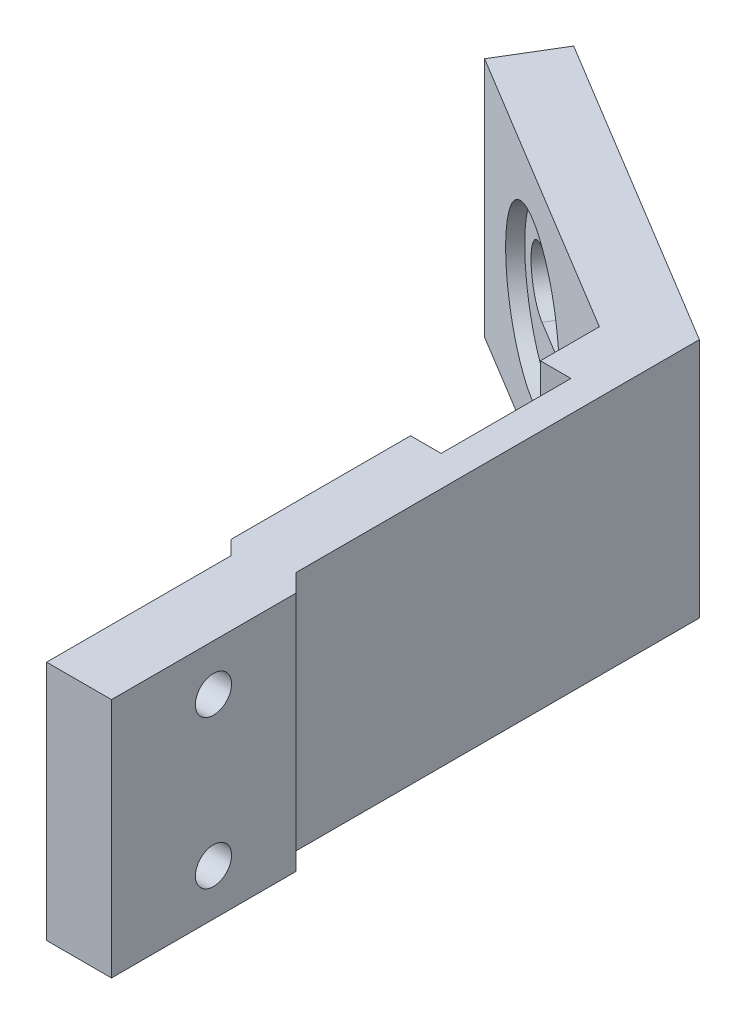
SolidWorks part; units mm, degrees
ref_plane "Front Plane" through (0, 0, 0) normal (0, 0, 1) x (1, 0, 0)
ref_plane "Top Plane" through (0, 0, 0) normal (0, 1, 0) x (1, 0, 0)
ref_plane "Right Plane" through (0, 0, 0) normal (1, 0, 0) x (0, 0, -1)
ref_plane "PY -20.700" through (0, -20.7, 0) normal (0, 1, 0) x (1, 0, 0)
sketch "leg and pad sketch" plane through (0, -20.7, 0) normal (0, 1, 0) x (1, 0, 0)
  line L0 (0.4, 29.7586) -> (0.4, -9.98)
  line L1 (0.4, -9.98) -> (1.92, -11.5)
  line L2 (1.92, -11.5) -> (1.92, -31.37)
  line L3 (1.92, -31.37) -> (8.92, -31.37)
  line L4 (8.92, -31.37) -> (8.92, -11.5)
  line L5 (8.92, -11.5) -> (7, -9.58)
  line L6 (7, -9.58) -> (7, 33.9514)
  line L7 (7, 33.9514) -> (-27.2048, 54.5947)
  line L8 (-27.2048, 54.5947) -> (-30.8218, 48.6015)
  line L9 (-30.8218, 48.6015) -> (0.4, 29.7586)
extrude "leg and pad" add sketch "leg and pad sketch" along normal mid plane 26
ref_plane "PX 1.350" through (1.35, 0, 0) normal (1, 0, 0) x (0, 0, -1)
sketch "screw head relief sketch" plane through (1.35, 0, 0) normal (1, 0, 0) x (0, 0, -1)
  line L0 (23.4, -12.7) -> (23.4, -6.7)
  line L1 (23.4, -6.7) -> (9.4, -6.7)
  line L2 (9.4, -6.7) -> (9.4, -12.7)
  line L3 (9.4, -12.7) -> (23.4, -12.7)
extrude "screw head relief" cut sketch "screw head relief sketch" against normal mid plane 4.7
sketch "insert flange relief sketch" plane through (0, -20.7, 0) normal (0, 1, 0) x (1, 0, 0)
  line L0 (-18.3249, 39.8914) -> (-17.0331, 42.0318)
  line L1 (-17.0331, 42.0318) -> (-9.7557, 37.6398)
  line L2 (-9.7557, 37.6398) -> (-11.0475, 35.4994)
  line L3 (-11.0475, 35.4994) -> (-18.3249, 39.8914)
revolve "insert flange relief" cut sketch "insert flange relief sketch" angle 360 about L0
sketch "M6 slot end 1 sketch" plane through (0, -20.7, 0) normal (0, 1, 0) x (1, 0, 0)
  line L0 (-20.8933, 41.4415) -> (-16.243, 49.147)
  line L1 (-16.243, 49.147) -> (-13.2464, 47.3385)
  line L2 (-13.2464, 47.3385) -> (-17.8968, 39.633)
  line L3 (-17.8968, 39.633) -> (-20.8933, 41.4415)
revolve "M6 slot end 1" cut sketch "M6 slot end 1 sketch" angle 360 about L0
sketch "M6 slot end 2 sketch" plane through (0, -20.7, 0) normal (0, 1, 0) x (1, 0, 0)
  line L0 (-15.7564, 38.3413) -> (-11.106, 46.0467)
  line L1 (-11.106, 46.0467) -> (-8.1094, 44.2382)
  line L2 (-8.1094, 44.2382) -> (-12.7598, 36.5328)
  line L3 (-12.7598, 36.5328) -> (-15.7564, 38.3413)
revolve "M6 slot end 2" cut sketch "M6 slot end 2 sketch" angle 360 about L0
sketch "M6 slot middle sketch" plane through (0, -20.7, 0) normal (0, 1, 0) x (1, 0, 0)
  line L0 (-15.7564, 38.3413) -> (-20.8933, 41.4415)
  line L1 (-20.8933, 41.4415) -> (-16.243, 49.147)
  line L2 (-16.243, 49.147) -> (-11.106, 46.0467)
  line L3 (-11.106, 46.0467) -> (-15.7564, 38.3413)
extrude "M6 slot middle" cut sketch "M6 slot middle sketch" against normal mid plane 7
ref_plane "PX 5.420" through (5.42, 0, 0) normal (1, 0, 0) x (0, 0, -1)
sketch "screw holes sketch" plane through (5.42, 0, 0) normal (1, 0, 0) x (0, 0, -1)
  circle A0 centre (-20.375, -28.7) radius 1.95
  circle A1 centre (-20.375, -12.7) radius 1.95
extrude "screw holes" cut sketch "screw holes sketch" against normal mid plane 9
equation "\"diffL\" = 608.8mm"
equation "\"diffW\" = 329.4mm"
equation "\"diffT\" = 2.9mm"
equation "\"chanSlotW\" = 12.9mm"
equation "\"chanSlotDepth\" = 11.13mm"
equation "\"chanFloor\" = 1.57mm"
equation "\"chanLeg\" = 12.7mm"
equation "\"lightL\" = 605mm"
equation "\"lightW\" = 331mm"
equation "\"lightH\" = 92mm"
equation "\"lightSideFlat\" = 30mm"
equation "\"lightSlopeLen\" = 33.1mm"
equation "\"lightWingDepth\" = 47.9mm"
equation "\"lightWingFlat\" = 90.2mm"
equation "\"lightChanW\" = 99.6mm"
equation "\"lightChanStand\" = 44.1mm"
equation "\"insFlangeD\" = 12.3mm"
equation "\"insFromEnd\" = 20.7mm"
equation "\"insUpSlope\" = 20.8mm"
equation "\"gaugeH\" = 10mm"
equation "\"gaugeStepLen\" = 14mm"
equation "\"gaugeStepW0\" = 13.1mm"
equation "\"gaugeStepDW\" = 0.2mm"
equation "\"gaugeSteps\" = 5mm"
equation "\"gaugeHandleLen\" = 30mm"
equation "\"gaugeHandleW\" = 24mm"
equation "\"gaugeSlot0\" = 3mm"
equation "\"gaugeSlotD\" = 0.1mm"
equation "\"gaugeSlotDepth\" = 8mm"
equation "\"gap\" = 25.4mm"
equation "\"edgeL\" = 1mm"
equation "\"edgeW\" = 0.75mm"
equation "\"proud\" = 1.5mm"
equation "\"seatClr\" = 0.15mm"
equation "\"tongueClrZ\" = 0.1mm"
equation "\"tongueClrX\" = 0.25mm"
equation "\"tongueLen\" = 30mm"
equation "\"armSide\" = 45mm"
equation "\"armEnd\" = 20mm"
equation "\"cornerCham\" = 3mm"
equation "\"brkW\" = 26mm"
equation "\"brkT\" = 7mm"
equation "\"brkSeatClr\" = 0.2mm"
equation "\"brkScrewSpan\" = 16mm"
equation "\"pilotD\" = 2.7mm"
equation "\"pilotDepth\" = 10mm"
equation "\"screwClrD\" = 3.9mm"
equation "\"jogBelow\" = 4mm"
equation "\"padT\" = 7mm"
equation "\"padLen\" = 31mm"
equation "\"m6Clr\" = 7mm"
equation "\"m6Slot\" = 3mm"
equation "\"flangeRelD\" = 17mm"
equation "\"flangeRelDepth\" = 1.5mm"
equation "\"relLen\" = 7mm"
equation "\"relDepth\" = 4mm"
equation "\"relLand\" = 2mm"
equation "\"knockN\" = 100mm"
equation "\"petgcfE\" = 3000mm"
equation "\"mockExtent\" = 110mm"
equation "\"relZnear\" = 9.4mm"
equation "\"relZfar\" = 23.4mm"
equation "\"headD\" = 8mm"
equation "\"headH\" = 2.5mm"
equation "\"headFromEnd\" = 6.8mm"
equation "\"headBack\" = 16.4mm"
equation "\"sideClr\" = 0.4mm"
